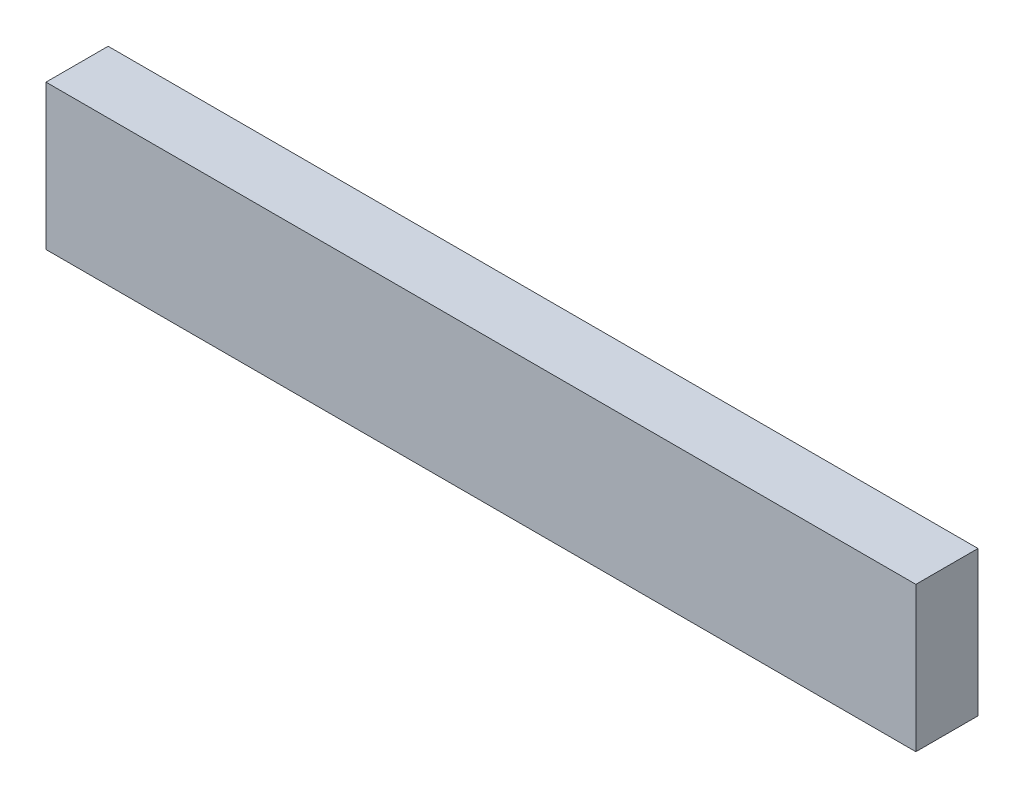
SolidWorks part; units mm, degrees
material "Cedar"
ref_plane "Front Plane" through (0, 0, 0) normal (0, 0, 1) x (1, 0, 0)
ref_plane "Top Plane" through (0, 0, 0) normal (0, 1, 0) x (1, 0, 0)
ref_plane "Right Plane" through (0, 0, 0) normal (1, 0, 0) x (0, 0, -1)
sketch "Sketch3" plane through (0, 0, 0) normal (1, 0, 0) x (0, 0, -1)
  line L1 (-19.05, -44.45) -> (19.05, -44.45)
  line L2 (-19.05, -44.45) -> (-19.05, 44.45)
  line L3 (-19.05, 44.45) -> (19.05, 44.45)
  line L4 (19.05, -44.45) -> (19.05, 44.45)
  line L5 (-19.05, -44.45) -> (19.05, 44.45) construction
  line L6 (-19.05, 44.45) -> (19.05, -44.45) construction
  point P0 (0, 0)
  dimension "D1" = 38.1
  dimension "D2" = 88.9
extrude "Boss-Extrude1" add sketch "Sketch3" along normal blind 266.7 and the other way blind 266.7
